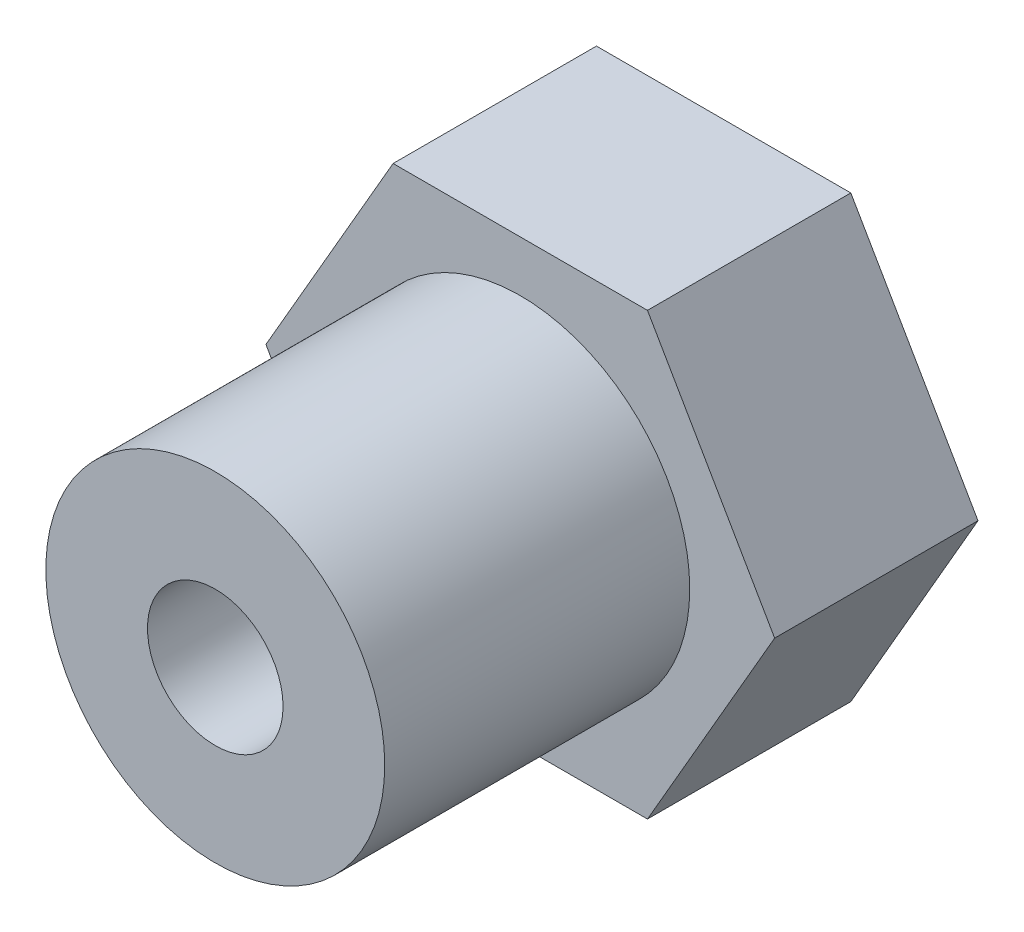
SolidWorks part; units mm, degrees
material "Aluminum Bronze"
ref_plane "Front Plane" through (0, 0, 0) normal (0, 0, 1) x (1, 0, 0)
ref_plane "Top Plane" through (0, 0, 0) normal (0, 1, 0) x (1, 0, 0)
ref_plane "Right Plane" through (0, 0, 0) normal (1, 0, 0) x (0, 0, -1)
sketch "Sketch2" plane through (0, 0, 0) normal (0, 0, 1) x (1, 0, 0)
  line L1 (7.5056, 0) -> (3.7528, 6.5)
  line L2 (3.7528, 6.5) -> (-3.7528, 6.5)
  line L3 (-3.7528, 6.5) -> (-7.5056, 0)
  line L4 (-7.5056, 0) -> (-3.7528, -6.5)
  line L5 (-3.7528, -6.5) -> (3.7528, -6.5)
  line L6 (3.7528, -6.5) -> (7.5056, 0)
  circle A0 centre (0, 0) radius 6.5 construction
  circle A1 centre (0, 0) radius 5
  circle A2 centre (0, 0) radius 2
  point P11 (0, 0)
  dimension "D2" = 10
  dimension "D3" = 4
  dimension "D1" = 13
extrude "Boss-Extrude1" add sketch "Sketch2" against normal blind 6 contours L5 L6 L1 L2 L3 L4 A1 | A1 A2 region at (5.4572, -3.1507, 0) region at (-4.8586, 0, 0)
extrude "Boss-Extrude2" add sketch "Sketch2<3>" along normal blind 9 contours A1 A2 region at (-4.8586, 0, 0)
sketch "Sketch2<3>" plane through (0, 0, 0) normal (0, 0, 1) x (1, 0, 0) same geometry as "Sketch2"
cosmetic thread "Cosmetic Thread2" parameters "D2"=8.344
